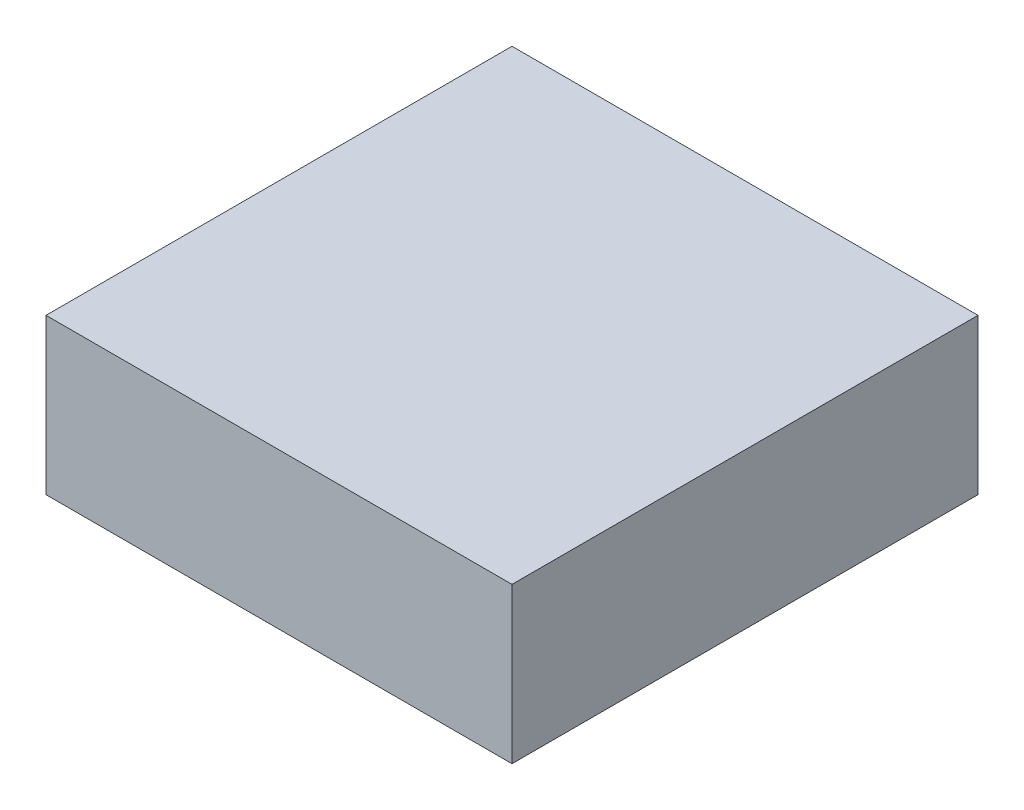
SolidWorks part; units mm, degrees
ref_plane "Piano frontale" through (0, 0, 0) normal (0, 0, 1) x (1, 0, 0)
ref_plane "Piano superiore" through (0, 0, 0) normal (0, 1, 0) x (1, 0, 0)
ref_plane "Piano destro" through (0, 0, 0) normal (1, 0, 0) x (0, 0, -1)
sketch "Schizzo1" plane through (0, 0, 0) normal (0, 1, 0) x (1, 0, 0)
  line L1 (-6.6108, 10.6348) -> (-3.6108, 10.6348)
  line L2 (-6.6108, 10.6348) -> (-6.6108, 7.6348)
  line L3 (-6.6108, 7.6348) -> (-3.6108, 7.6348)
  line L4 (-3.6108, 10.6348) -> (-3.6108, 7.6348)
  dimension "D1" = 3
  dimension "D2" = 3
extrude "Estrusione-Estrusione1" add sketch "Schizzo1" along normal blind 1
